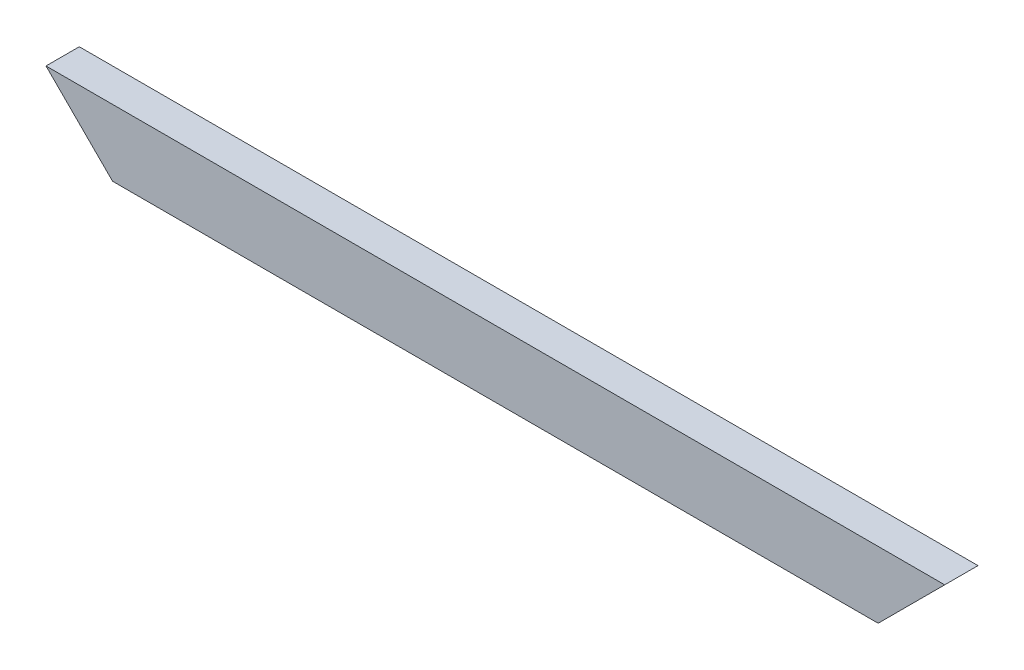
SolidWorks part; units mm, degrees
ref_plane "Front Plane" through (0, 0, 0) normal (0, 0, 1) x (1, 0, 0)
ref_plane "Top Plane" through (0, 0, 0) normal (0, 1, 0) x (1, 0, 0)
ref_plane "Right Plane" through (0, 0, 0) normal (1, 0, 0) x (0, 0, -1)
sketch "Sketch1" plane through (0, 0, 0) normal (1, 0, 0) x (0, 0, -1)
  line L1 (-9.525, -22.225) -> (9.525, -22.225)
  line L2 (-9.525, -22.225) -> (-9.525, 22.225)
  line L3 (-9.525, 22.225) -> (9.525, 22.225)
  line L4 (9.525, -22.225) -> (9.525, 22.225)
  line L5 (-9.525, -22.225) -> (9.525, 22.225) construction
  line L6 (-9.525, 22.225) -> (9.525, -22.225) construction
  line L7 (-12.7, -25.4) -> (12.7, -25.4)
  line L8 (-12.7, -25.4) -> (-12.7, 25.4)
  line L9 (-12.7, 25.4) -> (12.7, 25.4)
  line L10 (12.7, -25.4) -> (12.7, 25.4)
  line L11 (-12.7, -25.4) -> (12.7, 25.4) construction
  line L12 (-12.7, 25.4) -> (12.7, -25.4) construction
  point P0 (0, 0)
  point P6 (0, 0)
  dimension "D1" = 25.4
  dimension "D2" = 50.8
  dimension "D3" = 3.175
  dimension "D4" = 3.175
extrude "Boss-Extrude1" add sketch "Sketch1" along normal mid plane 685.8
sketch "Sketch2" plane through (0, 0, -12.7) normal (0, 0, -1) x (-1, 0, 0)
  line L0 (342.9, 25.4) -> (292.1, -25.4)
  line L1 (-342.9, -25.4) -> (342.9, -25.4) construction
  line L2 (-342.9, 25.4) -> (342.9, 25.4) construction
  line L3 (0, 13.97) -> (0, -13.97) construction
  line L4 (-342.9, 25.4) -> (-292.1, -25.4)
  line M2 (342.9, -25.4) -> (342.9, 25.4)
  line M4 (-342.9, 25.4) -> (-342.9, -25.4)
  line M5 (-342.9, -25.4) -> (342.9, -25.4)
  dimension "D1" = 45
extrude "Cut-Extrude1" cut sketch "Sketch2" against normal through all and the other way through all contours L0 M2 M5 | L4 M4 M5 region at (-325.9667, -8.4667, -12.7) region at (325.9667, -8.4667, -12.7)
